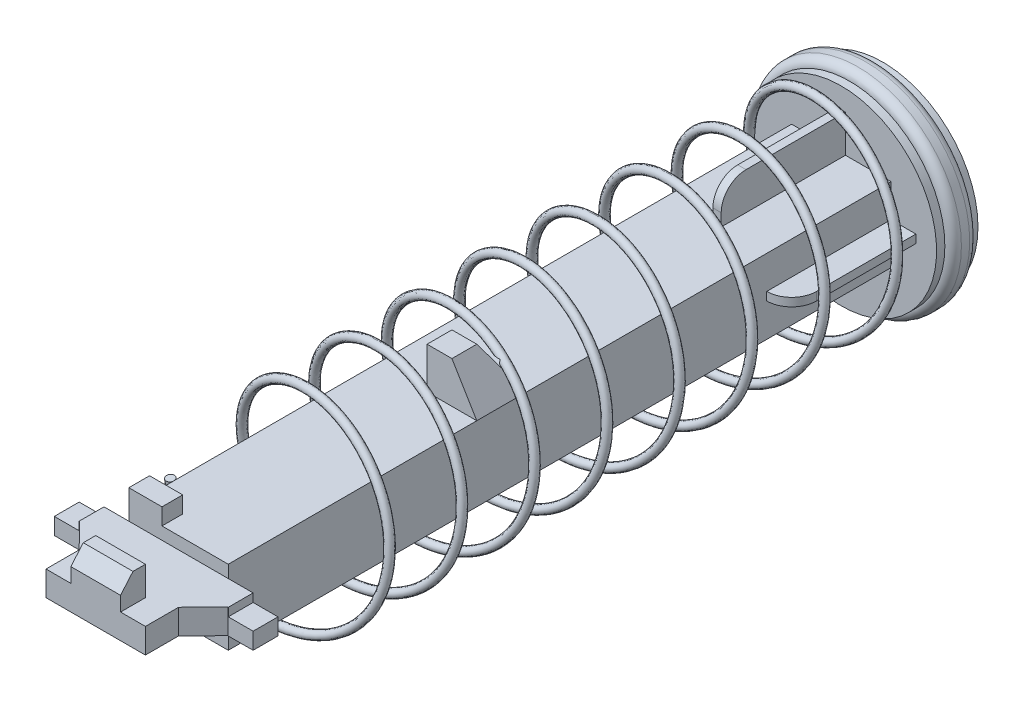
SolidWorks part; units mm, degrees
ref_plane "Front Plane" through (0, 0, 0) normal (0, 0, 1) x (1, 0, 0)
ref_plane "Top Plane" through (0, 0, 0) normal (0, 1, 0) x (1, 0, 0)
ref_plane "Right Plane" through (0, 0, 0) normal (1, 0, 0) x (0, 0, -1)
sketch "Sketch2" plane through (0, 0, 0) normal (0, 0, 1) x (1, 0, 0)
  circle A0 centre (0, 0) radius 11.5
  dimension "D1" = 23
extrude "Boss-Extrude1" add sketch "Sketch2" along normal blind 1
sketch "Sketch3" plane through (0, 0, 1) normal (0, 0, 1) x (1, 0, 0)
  circle A0 centre (0, 0) radius 12.5
  dimension "D1" = 25
extrude "Boss-Extrude2" add sketch "Sketch3" along normal blind 3
fillet "Fillet1" radius 1 2 edges at (12.5, 0, 4) (12.5, 0, 1)
sketch "Sketch4" plane through (0, 0, 4) normal (0, 0, 1) x (1, 0, 0)
  circle A0 centre (0, 0) radius 11.5 construction
  circle A1 centre (0, 0) radius 11.5
extrude "Boss-Extrude3" add sketch "Sketch4" along normal blind 1
sketch "Sketch5" plane through (0, 0, 5) normal (0, 0, 1) x (1, 0, 0)
  line L0 (0, 0) -> (6, 0) construction
  line L1 (2.75, 0) -> (-2.75, 0) construction
  line L2 (6, 0) -> (6, -4.5) construction
  line L3 (6, -4.5) -> (-6, -4.5)
  line L4 (0, -2.75) -> (0, 2.75) construction
  line L5 (6, 4.5) -> (6, -4.5)
  line L6 (-6, 4.5) -> (-6, -4.5)
  line L7 (6, 4.5) -> (-6, 4.5)
  point P10 (0, -4.5)
  point P13 (-6, 0)
extrude "Boss-Extrude4" add sketch "Sketch5" along normal blind 80
sketch "Sketch6" plane through (0, 0, 5) normal (0, 0, 1) x (1, 0, 0)
  line L0 (-6, 0) -> (-9, 0)
  line L1 (-9, 0) -> (-9, 0.5172)
  line L2 (-9, 0.5172) -> (-9, -0.4828)
  line L3 (-9, -0.4828) -> (-6, -0.4828)
  line L4 (-6, 4.5) -> (-6, -4.5)
  line L5 (-6, -4.5) -> (6, -4.5)
  line L6 (6, -4.5) -> (6, 4.5)
  line L7 (6, 4.5) -> (-6, 4.5)
  line L8 (-6, 4.5) -> (-6, -4.5)
  line L9 (-6, -4.5) -> (6, -4.5)
  line L10 (6, -4.5) -> (6, 4.5)
  line L11 (6, 4.5) -> (-6, 4.5)
  line L12 (-6, -0.4828) -> (-6, 0.5172)
  line L13 (-6, 0.5172) -> (-9, 0.5172)
  line L14 (0, -13.75) -> (0, 13.75) construction
  line L15 (6, 0.5172) -> (9, 0.5172)
  line L16 (9, -0.4828) -> (6, -0.4828)
  line L17 (9, 0.5172) -> (9, -0.4828)
  line L19 (0.5, -9) -> (-0.5, -9)
  line L20 (-0.5, -9) -> (-0.5, -4.5)
  line L21 (-0.5, -4.5) -> (1.2146, -4.5)
  line L22 (0.5, -9) -> (0.5, -4.5)
  line L23 (13.75, 0) -> (-13.75, 0) construction
  line L24 (0.5, 9) -> (0.5, 4.5)
  line L25 (0.5, 9) -> (-0.5, 9)
  line L26 (-0.5, 9) -> (-0.5, 4.5)
  dimension "D2" = 1
  dimension "D1" = 0
extrude "Boss-Extrude5" add sketch "Sketch6" along normal blind 15 contours L25 L26 L11 L24 | L17 L15 L10 L16 | L19 L22 L21 L20 | L2 L3 L12 L13
fillet "Fillet2" radius 3 4 edges at (9, 0.0172, 20) (0, -9, 20) (0, 9, 20) (-9, 0.0172, 20)
sketch "Sketch7" plane through (0, 0, 85) normal (0, 0, 1) x (1, 0, 0)
  line L0 (-6, 0) -> (-12, 0)
  line L1 (13.75, 0) -> (-13.75, 0) construction
  line L2 (-6, 0) -> (6, 0)
  line L3 (0, -13.75) -> (0, 13.75) construction
  line L4 (-6, 4.5) -> (-6, -4.5)
  line L5 (-6, -4.5) -> (6, -4.5)
  line L6 (6, -4.5) -> (6, 4.5)
  line L7 (6, 4.5) -> (-6, 4.5)
  line L8 (-6, 4.5) -> (-6, -4.5)
  line L9 (-6, -4.5) -> (6, -4.5)
  line L10 (6, -4.5) -> (6, 4.5)
  line L11 (6, 4.5) -> (-6, 4.5)
  line L12 (6, 0) -> (12, 0)
  line L13 (-12, 0) -> (-12, 2)
  line L14 (-12, 2) -> (12, 2)
  line L15 (12, 2) -> (12, 0)
  point P15 (0, 0)
  dimension "D2" = 12
  dimension "D3" = 2
  dimension "D1" = 0
sketch "Sketch11" plane through (0, 0, 5) normal (0, 0, 1) x (1, 0, 0)
  circle A0 centre (0, 0) radius 11
curve "Helix/Spiral1" pitch 8.75 height 70 turns 8
sweep "Sweep1" add path "Helix/Spiral1" parameters "D3"=1
sketch "Sketch28" plane through (0, 0, 0) normal (0, 0, -1) x (-1, 0, 0)
  circle A0 centre (0, 0) radius 7.5
  dimension "D2" = 15
extrude "Cut-Extrude3" cut sketch "Sketch28" against normal blind 3
fillet "Fillet3" radius 0.5 1 edges at (-7.5, 0, 0)
sketch "Sketch33" plane through (0, 0, 85) normal (0, 0, 1) x (1, 0, 0)
  line L0 (6, 0) -> (9, 0)
  line L1 (6, 0) -> (12, 0) construction
  line L2 (9, 0) -> (9, 3)
  line L3 (9, 3) -> (6, 3)
  line L4 (-6, 4.5) -> (-6, -4.5)
  line L5 (-6, -4.5) -> (6, -4.5)
  line L6 (6, -4.5) -> (6, 4.5)
  line L7 (6, 4.5) -> (-6, 4.5)
  line L8 (-6, 3) -> (-6, -4.5)
  line L9 (-6, -4.5) -> (6, -4.5)
  line L10 (6, -4.5) -> (6, 3)
  line L11 (6, 3) -> (-6, 3)
  line L12 (9, 0) -> (12, 0)
  line L13 (12, 0) -> (12, 2)
  line L14 (12, 2) -> (9, 2)
  line L15 (0, -13.75) -> (0, 13.75) construction
  line L16 (-9, 3) -> (-6, 3)
  line L17 (-9, 0) -> (-9, 3)
  line L18 (-12, 2) -> (-9, 2)
  line L19 (-12, 0) -> (-12, 2)
  line L20 (-9, 0) -> (-12, 0)
  line L21 (-6, 0) -> (-9, 0)
  line L22 (6, 0) -> (-6, 0)
  line L23 (6, 4.5) -> (-6, 4.5) construction
  point P5 (6, 4.5)
  point P8 (6, 0)
  point P23 (6, 4.5)
  point P24 (-6, 4.5)
  line M11 (-6, 4.5) -> (-6, -4.5)
  line M13 (6, -4.5) -> (6, 4.5)
  line M14 (6, 4.5) -> (-6, 4.5)
  dimension "D2" = 1.5
  dimension "D3" = 2
  dimension "D1" = 0
extrude "Boss-Extrude6" add sketch "Sketch33" along normal blind 6 contours L13 L14 L2 L12 | L2 L3 L0 M13 | L22 M13 M14 M11 | L21 L16 L17 M11 | L20 L17 L18 L19
sketch "Sketch34" plane through (0, 0, 91) normal (0, 0, 1) x (1, 0, 0)
  line L0 (-12, 2) -> (12, 2) construction
  line L1 (-12, 2) -> (12, 2)
  line L2 (6, -4.5) -> (6, 4.5) construction
  line L3 (6, -4.5) -> (6, 4.5)
  line L4 (-6, 4.5) -> (-6, -4.5) construction
  line L5 (-6, 4.5) -> (-6, -4.5)
  line L8 (12, 0) -> (12, 2)
  line L9 (12, 2) -> (9, 2)
  line L10 (9, 2) -> (9, 3)
  line L11 (9, 3) -> (-9, 3)
  line L12 (-9, 3) -> (-9, 2)
  line L13 (-9, 2) -> (-12, 2)
  line L14 (-12, 2) -> (-12, 0)
  line L15 (-12, 0) -> (12, 0)
  line L16 (12, 0) -> (12, 2)
  line L17 (12, 2) -> (9, 2)
  line L18 (9, 2) -> (9, 3)
  line L19 (9, 3) -> (-9, 3)
  line L20 (-9, 3) -> (-9, 2)
  line L21 (-9, 2) -> (-12, 2)
  line L22 (-12, 2) -> (-12, 0)
  line L23 (-12, 0) -> (12, 0)
  line M12 (9, 3) -> (-9, 3)
  line M16 (-12, 0) -> (12, 0)
  dimension "D1" = 0
extrude "Boss-Extrude7" add sketch "Sketch34" along normal blind 4 contours L1 L5 L3 M16 | L5 L1 L3 M12
sketch "Sketch35" plane through (0, 4.5, 0) normal (0, 1, 0) x (1, 0, 0)
  line L0 (0, -95) -> (0, -92)
  line L1 (6, -95) -> (-6, -95) construction
  line L2 (3, -92) -> (-3, -92)
  line L3 (-3, -92) -> (-3, -95)
  line L4 (6, -95) -> (-6, -95)
  line L5 (3, -92) -> (3, -95)
  line L14 (-6, -85) -> (6, -85)
  line L15 (-6, -85) -> (6, -85)
  line L21 (-0.5, -20) -> (-0.5, -5)
  line L22 (-0.5, -5) -> (-6, -5)
  line L23 (-6, -5) -> (-6, -85)
  line L33 (6, -85) -> (6, -5)
  line L34 (6, -5) -> (0.5, -5)
  line L35 (0.5, -5) -> (0.5, -20)
  line L36 (0.5, -20) -> (-0.5, -20)
  line L37 (-0.5, -20) -> (-0.5, -5)
  line L38 (-0.5, -5) -> (-6, -5)
  line L39 (-6, -5) -> (-6, -85)
  line L49 (6, -85) -> (6, -5)
  line L50 (6, -5) -> (0.5, -5)
  line L51 (0.5, -5) -> (0.5, -20)
  line L52 (0.5, -20) -> (-0.5, -20)
  dimension "D2" = 3
  dimension "D3" = 3
  dimension "D1" = 0
extrude "Boss-Extrude8" add sketch "Sketch35" along normal blind 2
sketch "Sketch36" plane through (-3, 0, 0) normal (-1, 0, 0) x (0, 0, 1)
  line L0 (95, 4.5) -> (93, 6.5)
  line L1 (92, 6.5) -> (95, 6.5) construction
  line L6 (92, 4.5) -> (95, 4.5)
  line L7 (92, 4.5) -> (95, 4.5)
  line L8 (95, 6.5) -> (92, 6.5)
  line L9 (92, 6.5) -> (92, 4.5)
  line L12 (95, 6.5) -> (92, 6.5)
  line L13 (92, 6.5) -> (92, 4.5)
  line L14 (95, 4.5) -> (95, 6.5)
  line L15 (95, 4.5) -> (95, 6.5)
  dimension "D1" = 0
sketch "Sketch37" plane through (0, 4.5, 0) normal (0, 1, 0) x (1, 0, 0)
  line L0 (-6, -85) -> (-2, -85)
  line L1 (6, -85) -> (-6, -85) construction
  line L2 (-2, -85) -> (-2, -82.5)
  line L3 (-2, -82.5) -> (-6, -82.5)
  line L20 (-3, -92) -> (3, -92)
  line L21 (3, -92) -> (3, -95)
  line L22 (3, -95) -> (6, -95)
  line L23 (6, -95) -> (6, -91)
  line L24 (6, -91) -> (9, -91)
  line L25 (9, -91) -> (9, -85)
  line L26 (9, -85) -> (6, -85)
  line L27 (6, -85) -> (6, -5)
  line L28 (6, -5) -> (0.5, -5)
  line L29 (0.5, -5) -> (0.5, -20)
  line L30 (0.5, -20) -> (-0.5, -20)
  line L31 (-0.5, -20) -> (-0.5, -5)
  line L32 (-0.5, -5) -> (-6, -5)
  line L33 (-6, -5) -> (-6, -85)
  line L34 (-6, -85) -> (-9, -85)
  line L35 (-9, -85) -> (-9, -91)
  line L36 (-9, -91) -> (-6, -91)
  line L37 (-6, -91) -> (-6, -95)
  line L38 (-6, -95) -> (-3, -95)
  line L39 (-3, -95) -> (-3, -92)
  line L40 (-3, -92) -> (3, -92)
  line L41 (3, -92) -> (3, -95)
  line L42 (3, -95) -> (6, -95)
  line L43 (6, -95) -> (6, -91)
  line L44 (6, -91) -> (9, -91)
  line L45 (9, -91) -> (9, -85)
  line L46 (9, -85) -> (6, -85)
  line L47 (6, -85) -> (6, -5)
  line L48 (6, -5) -> (0.5, -5)
  line L49 (0.5, -5) -> (0.5, -20)
  line L50 (0.5, -20) -> (-0.5, -20)
  line L51 (-0.5, -20) -> (-0.5, -5)
  line L52 (-0.5, -5) -> (-6, -5)
  line L53 (-6, -5) -> (-6, -85)
  line L54 (-6, -85) -> (-9, -85)
  line L55 (-9, -85) -> (-9, -91)
  line L56 (-9, -91) -> (-6, -91)
  line L57 (-6, -91) -> (-6, -95)
  line L58 (-6, -95) -> (-3, -95)
  line L59 (-3, -95) -> (-3, -92)
  line M36 (-6, -5) -> (-6, -85)
  dimension "D2" = 4
  dimension "D3" = 2.5
  dimension "D1" = 0
sketch "Sketch44" plane through (0, 3, 0) normal (0, 1, 0) x (1, 0, 0)
  line L4 (3, -95) -> (3, -92)
  line L5 (3, -92) -> (-3, -92)
  line L6 (-3, -92) -> (-3, -95)
  line L7 (-3, -95) -> (3, -95)
  line L8 (3, -95) -> (3, -92)
  line L9 (3, -92) -> (-3, -92)
  line L10 (-3, -92) -> (-3, -95)
  line L11 (-3, -95) -> (3, -95)
  dimension "D1" = 0
extrude "Boss-Extrude12" add sketch "Sketch44" along normal blind 3
extrude "Boss-Extrude9" add sketch "Sketch37" along normal blind 2 contours L2 L3 L0 M36
sketch "Sketch38" plane through (0, 0, 0) normal (0, -1, 0) x (1, 0, 0)
  line L0 (-12, 88) -> (-8.9391, 88)
  line L1 (-8.9391, 88) -> (-6, 91)
  line L2 (0, -13.75) -> (0, 13.75) construction
  line L3 (12, 88) -> (8.9391, 88)
  line L4 (8.9391, 88) -> (6, 91)
  line L10 (-12, 85) -> (-6, 85)
  line L11 (-6, 85) -> (6, 85)
  line L12 (6, 85) -> (12, 85)
  line L13 (12, 85) -> (12, 91)
  line L14 (12, 91) -> (6, 91)
  line L15 (6, 91) -> (6, 95)
  line L16 (6, 95) -> (-6, 95)
  line L17 (-6, 95) -> (-6, 91)
  line L18 (-6, 91) -> (-12, 91)
  line L19 (-12, 91) -> (-12, 85)
  line L20 (-12, 85) -> (-6, 85)
  line L21 (-6, 85) -> (6, 85)
  line L22 (6, 85) -> (12, 85)
  line L23 (12, 85) -> (12, 91)
  line L24 (12, 91) -> (6, 91)
  line L25 (6, 91) -> (6, 95)
  line L26 (6, 95) -> (-6, 95)
  line L27 (-6, 95) -> (-6, 91)
  line L28 (-6, 91) -> (-12, 91)
  line L29 (-12, 91) -> (-12, 85)
  line M16 (12, 85) -> (12, 91)
  line M17 (12, 91) -> (6, 91)
  line M21 (-6, 91) -> (-12, 91)
  line M22 (-12, 91) -> (-12, 85)
  dimension "D1" = 0
extrude "Cut-Extrude5" cut sketch "Sketch38" against normal through all contours L0 L1 M21 M22 | L4 L3 M16 M17
sketch "Sketch39" plane through (0, 4.5, 0) normal (0, 1, 0) x (1, 0, 0)
  line L0 (6, -85) -> (6, -55) construction
  line L1 (6, -55) -> (0, -55)
  line L2 (0, -55) -> (0, -49)
  line L3 (0, -49) -> (6, -49)
  line L39 (6, -85) -> (6, -5)
  line L40 (6, -5) -> (0.5, -5)
  line L41 (0.5, -5) -> (0.5, -20)
  line L42 (0.5, -20) -> (-0.5, -20)
  line L43 (-0.5, -20) -> (-0.5, -5)
  line L44 (-0.5, -5) -> (-6, -5)
  line L45 (-6, -5) -> (-6, -82.5)
  line L46 (-6, -82.5) -> (-2, -82.5)
  line L47 (-2, -82.5) -> (-2, -85)
  line L48 (-2, -85) -> (6, -85)
  line L64 (6, -85) -> (6, -5)
  line L65 (6, -5) -> (0.5, -5)
  line L66 (0.5, -5) -> (0.5, -20)
  line L67 (0.5, -20) -> (-0.5, -20)
  line L68 (-0.5, -20) -> (-0.5, -5)
  line L69 (-0.5, -5) -> (-6, -5)
  line L70 (-6, -5) -> (-6, -82.5)
  line L71 (-6, -82.5) -> (-2, -82.5)
  line L72 (-2, -82.5) -> (-2, -85)
  line L73 (-2, -85) -> (6, -85)
  line M45 (6, -85) -> (6, -5)
  dimension "D2" = 30
  dimension "D1" = 0
extrude "Boss-Extrude10" add sketch "Sketch39" along normal blind 5 contours L3 L2 L1 M45
ref_plane "Plane1" through (-11, 0, 75) normal (0, 0.9921, 0.1256) x (1, 0, 0)
sketch "Sketch41" plane through (6, 0, 0) normal (1, 0, 0) x (0, 0, -1)
  line L14 (-20, -0.4828) -> (-20, 0.5172)
  line L15 (-20, 0.5172) -> (-5, 0.5172)
  line L16 (-5, 0.5172) -> (-5, 4.5)
  line L17 (-5, 4.5) -> (-49, 4.5)
  line L18 (-49, 4.5) -> (-49, 9.5)
  line L19 (-49, 9.5) -> (-51.2775, 9.5)
  line L20 (-52.166, 9.5) -> (-55, 9.5)
  line L21 (-55, 9.5) -> (-55, 4.5)
  line L22 (-55, 4.5) -> (-85, 4.5)
  line L23 (-85, 3) -> (-85, 0)
  line L24 (-85, 0) -> (-85, -4.5)
  line L25 (-85, -4.5) -> (-5, -4.5)
  line L26 (-5, -4.5) -> (-5, -0.4828)
  line L27 (-5, -0.4828) -> (-20, -0.4828)
  line L28 (-20, -0.4828) -> (-20, 0.5172)
  line L29 (-20, 0.5172) -> (-5, 0.5172)
  line L30 (-5, 0.5172) -> (-5, 4.5)
  line L31 (-5, 4.5) -> (-49, 4.5)
  line L32 (-49, 4.5) -> (-49, 9.5)
  line L33 (-49, 9.5) -> (-51.2775, 9.5)
  line L35 (-55, 9.5) -> (-55, 4.5)
  line L36 (-55, 4.5) -> (-85, 4.5)
  line L37 (-85, 3) -> (-85, 0)
  line L38 (-85, 0) -> (-85, -4.5)
  line L39 (-85, -4.5) -> (-5, -4.5)
  line L40 (-5, -4.5) -> (-5, -0.4828)
  line L41 (-5, -0.4828) -> (-20, -0.4828)
  line L42 (-52.166, 9.5) -> (-55, 9.5)
  line L44 (-85, 4.5) -> (-85, 3)
  line L45 (-85, 4.5) -> (-85, 3)
  spline S1 degree 3 poles (-926.9008, -1787.5895) (-113.8712, 55.0699) (-48.5149, 14.3459) (-51.3604, 8.8518) (-51.4231, 8.7743) (-51.578, 8.6587) (-51.6729, 8.6207) (-51.8658, 8.6136) (-51.9637, 8.6463) (-52.1161, 8.7644) (-52.1724, 8.8479) (-52.2399, 9.0296) (-52.2519, 9.1269) (-51.6418, 17.1969) (76.414, 0.9324) (485.8245, -1914.3143) knots -7.601195 -7.601195 -7.601195 -7.601195 0.25 0.25 0.375 0.375 0.5 0.5 0.625 0.625 0.75 0.75 0.875 0.875 11.17069 11.17069 11.17069 11.17069 only from (-51.2775, 9.5) to (-52.166, 9.5)
  spline S2 degree 3 poles (-51.2775, 9.5) (-51.2066, 9.3181) (-51.2266, 9.1101) (-51.3604, 8.8518) (-51.4231, 8.7743) (-51.578, 8.6587) (-51.6729, 8.6207) (-51.8658, 8.6136) (-51.9637, 8.6463) (-52.1161, 8.7644) (-52.1724, 8.8479) (-52.2399, 9.0296) (-52.2519, 9.1269) (-52.2373, 9.3205) (-52.2111, 9.4137) (-52.166, 9.5) knots 0 0 0 0 0.25 0.25 0.375 0.375 0.5 0.5 0.625 0.625 0.75 0.75 0.875 0.875 1 1 1 1
  dimension "D1" = 0
sketch "Sketch42" plane through (0, 0, 55) normal (0, 0, 1) x (1, 0, 0)
  line L0 (6, 4.5) -> (3, 9.5)
  line L4 (0, 4.5) -> (6, 4.5)
  line L5 (6, 4.5) -> (6, 9.5)
  line L6 (6, 9.5) -> (0, 9.5)
  line L7 (0, 9.5) -> (0, 4.5)
  line L8 (0, 4.5) -> (6, 4.5)
  line L9 (6, 4.5) -> (6, 9.5)
  line L10 (6, 9.5) -> (0, 9.5)
  line L11 (0, 9.5) -> (0, 4.5)
  line M6 (6, 4.5) -> (6, 9.5)
  line M7 (6, 9.5) -> (0, 9.5)
  dimension "D1" = 0
extrude "Cut-Extrude6" cut sketch "Sketch42" against normal up to next contours L0 M6 M7
sketch "Sketch43" plane through (0, 0, 0) normal (-1, 0, 0) x (0, 0, 1)
  line L0 (52, 9.5) -> (49, 4.5)
  line L4 (49, 4.5) -> (55, 4.5)
  line L5 (55, 4.5) -> (55, 9.5)
  line L6 (55, 9.5) -> (49, 9.5)
  line L7 (49, 9.5) -> (49, 4.5)
  line L8 (49, 4.5) -> (55, 4.5)
  line L9 (55, 4.5) -> (55, 9.5)
  line L10 (55, 9.5) -> (49, 9.5)
  line L11 (49, 9.5) -> (49, 4.5)
  line M7 (55, 9.5) -> (49, 9.5)
  line M8 (49, 9.5) -> (49, 4.5)
  dimension "D1" = 0
extrude "Cut-Extrude7" cut sketch "Sketch43" against normal up to next contours L0 M7 M8
sketch "Sketch45" plane through (3, 0, 0) normal (1, 0, 0) x (0, 0, -1)
  line L0 (-93.5, 6.5) -> (-95, 4.75)
  line L4 (-95, 6.5) -> (-95, 3)
  line L5 (-95, 3) -> (-92, 3)
  line L6 (-92, 3) -> (-92, 6.5)
  line L7 (-92, 6.5) -> (-95, 6.5)
  line L8 (-95, 6.5) -> (-95, 3)
  line L9 (-95, 3) -> (-92, 3)
  line L10 (-92, 3) -> (-92, 6.5)
  line L11 (-92, 6.5) -> (-95, 6.5)
  line M5 (-95, 6.5) -> (-95, 3)
  line M8 (-92, 6.5) -> (-95, 6.5)
  dimension "D1" = 0
extrude "Cut-Extrude8" cut sketch "Sketch45" against normal up to next contours L0 M8 M5
